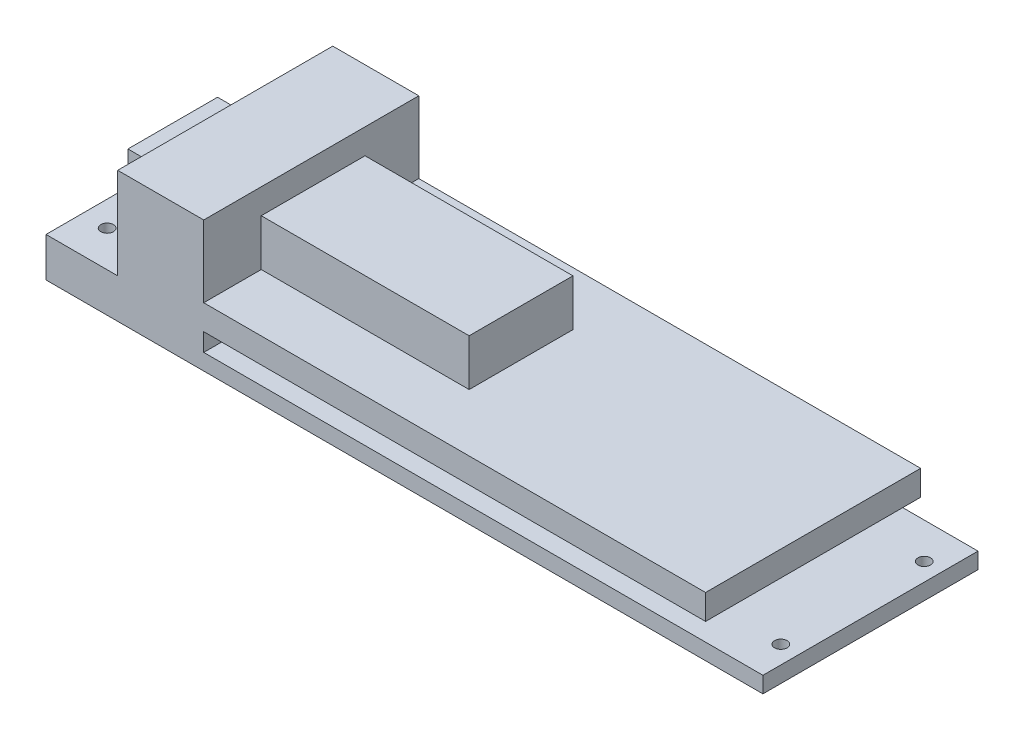
SolidWorks part; units mm, degrees
ref_plane "Front Plane" through (0, 0, 0) normal (0, 0, 1) x (1, 0, 0)
ref_plane "Top Plane" through (0, 0, 0) normal (0, 1, 0) x (1, 0, 0)
ref_plane "Right Plane" through (0, 0, 0) normal (1, 0, 0) x (0, 0, -1)
sketch "Sketch1" plane through (0, 0, 0) normal (0, 1, 0) x (1, 0, 0)
  line L0 (95, 6.4433) -> (95, -49993.5567) construction
  line L1 (-100, 30) -> (100, 30)
  line L2 (-100, 30) -> (-100, -30)
  line L3 (-100, -30) -> (100, -30)
  line L4 (100, 30) -> (100, -30)
  line L5 (-100, 30) -> (100, -30) construction
  line L6 (-100, -30) -> (100, 30) construction
  line L7 (45.8763, -20) -> (50045.8763, -20) construction
  line L8 (57.2165, 20) -> (50057.2165, 20) construction
  circle A0 centre (95, -20) radius 1.75
  circle A1 centre (95, 20) radius 1.75
  point P0 (0, 0)
  dimension "D6" = 3.5
  dimension "D1" = 200
  dimension "D2" = 60
  dimension "D3" = 5
  dimension "D4" = 10
  dimension "D5" = 10
extrude "Boss-Extrude1" add sketch "Sketch1" along normal blind 4.5
sketch "Sketch2" plane through (0, 4.5, 0) normal (0, 1, 0) x (1, 0, 0)
  line L0 (-100, -30) -> (100, -30) construction
  line L1 (-100, 30) -> (-80, 30)
  line L2 (-100, 30) -> (-100, -30)
  line L3 (-100, -30) -> (-80, -30)
  line L4 (-80, 30) -> (-80, -30)
  dimension "D1" = 20
extrude "Boss-Extrude2" add sketch "Sketch2" along normal blind 6.5
sketch "Sketch3" plane through (0, 4.5, 0) normal (0, 1, 0) x (1, 0, 0)
  line L0 (-80, -30) -> (-80, 30) construction
  line L1 (-80, 30) -> (-56, 30)
  line L2 (-80, 30) -> (-80, -30)
  line L3 (-80, -30) -> (-56, -30)
  line L4 (-56, 30) -> (-56, -30)
  line L5 (100, 30) -> (-80, 30) construction
  line L6 (-80, -30) -> (100, -30) construction
  dimension "D1" = 24
extrude "Boss-Extrude3" add sketch "Sketch3" along normal blind 32
ref_plane "Plane1" through (0, 19, 0) normal (0, 1, 0) x (1, 0, 0)
sketch "Sketch5" plane through (0, 19, 0) normal (0, 1, 0) x (1, 0, 0)
  line L0 (-74.2268, -0.4191) -> (-74.2268, 12.0809) construction
  line L2 (-74.2268, 12.0809) -> (-94.2268, 12.0809)
  line L3 (-74.2268, 12.0809) -> (-74.2268, -12.9191)
  line L4 (-74.2268, -12.9191) -> (-94.2268, -12.9191)
  line L5 (-94.2268, 12.0809) -> (-94.2268, -12.9191)
  dimension "D1" = 12.5
  dimension "D2" = 25
  dimension "D3" = 20
extrude "Boss-Extrude4" add sketch "Sketch5" along normal blind 7
ref_plane "Plane2" through (0, 9.5, 0) normal (0, 1, 0) x (1, 0, 0)
sketch "Sketch6" plane through (0, 9.5, 0) normal (0, 1, 0) x (1, 0, 0)
  line L0 (-56, -30) -> (100, -30) construction
  line L1 (-56, 30) -> (84, 30)
  line L2 (-56, 30) -> (-56, -30)
  line L3 (-56, -30) -> (84, -30)
  line L4 (84, 30) -> (84, -30)
  dimension "D1" = 140
extrude "Boss-Extrude5" add sketch "Sketch6" along normal blind 7
sketch "Sketch7" plane through (0, 16.5, 0) normal (0, 1, 0) x (1, 0, 0)
  line L0 (-56, 0) -> (-56, 15) construction
  line L1 (-56, 30) -> (-56, -30) construction
  line L3 (-56, 15) -> (2, 15)
  line L4 (-56, 15) -> (-56, -13.9538)
  line L5 (-56, -13.9538) -> (2, -13.9538)
  line L6 (2, 15) -> (2, -13.9538)
  dimension "D1" = 15
  dimension "D2" = 58
extrude "Boss-Extrude6" add sketch "Sketch7" along normal blind 13
sketch "Sketch8" plane through (0, 0, 0) normal (0, -1, 0) x (1, 0, 0)
  line L0 (-93, 11.8532) -> (-93, 50011.8532) construction
  line L1 (-96.8274, 20) -> (49903.1726, 20) construction
  line L2 (-96.6774, -20) -> (49903.3226, -20) construction
  line L3 (-100, -30) -> (-100, 30) construction
  line L4 (-100, 30) -> (100, 30) construction
  line L5 (100, -30) -> (-100, -30) construction
  circle A0 centre (-93, -20) radius 1.75
  circle A1 centre (-93, 19.9555) radius 1.75
  dimension "D4" = 3.5
  dimension "D1" = 7
  dimension "D2" = 10
  dimension "D3" = 10
extrude "Cut-Extrude1" cut sketch "Sketch8" against normal blind 13
